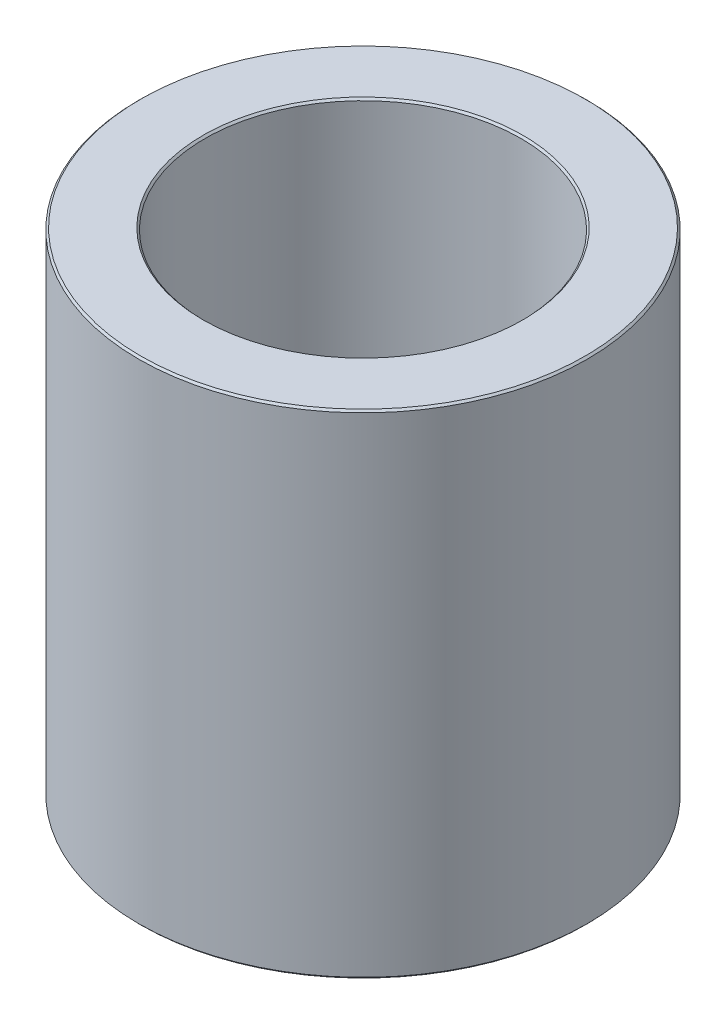
SolidWorks part; units mm, degrees
ref_plane "Front Plane" through (0, 0, 0) normal (0, 0, 1) x (1, 0, 0)
ref_plane "Top Plane" through (0, 0, 0) normal (0, 1, 0) x (1, 0, 0)
ref_plane "Right Plane" through (0, 0, 0) normal (1, 0, 0) x (0, 0, -1)
sketch "Sketch1" plane through (0, 0, 0) normal (0, 1, 0) x (1, 0, 0)
  circle A0 centre (0, 0) radius 52.5
  dimension "SLEEVE_OD" = 105
extrude "Boss-Extrude1" add sketch "Sketch1" along normal blind 115.3081
sketch "Sketch2" plane through (0, 0, 0) normal (0, 1, 0) x (1, 0, 0)
  circle A0 centre (0, 0) radius 37.0061
  dimension "BORE_D" = 74.0123
extrude "Cut-Extrude1" cut sketch "Sketch2" along normal through all
chamfer "Chamfer1" distance 0.4301 angle 46.175 4 edges at (0, 115.3081, 37.0061) (0, 0, 37.0061) (0, 0, 52.5) (0, 115.3081, 52.5) first distance on face at (0, 115.3081, 37.0061) first distance on face at (0, 0, 37.0061) first distance on face at (0, 115.3081, 52.5)
